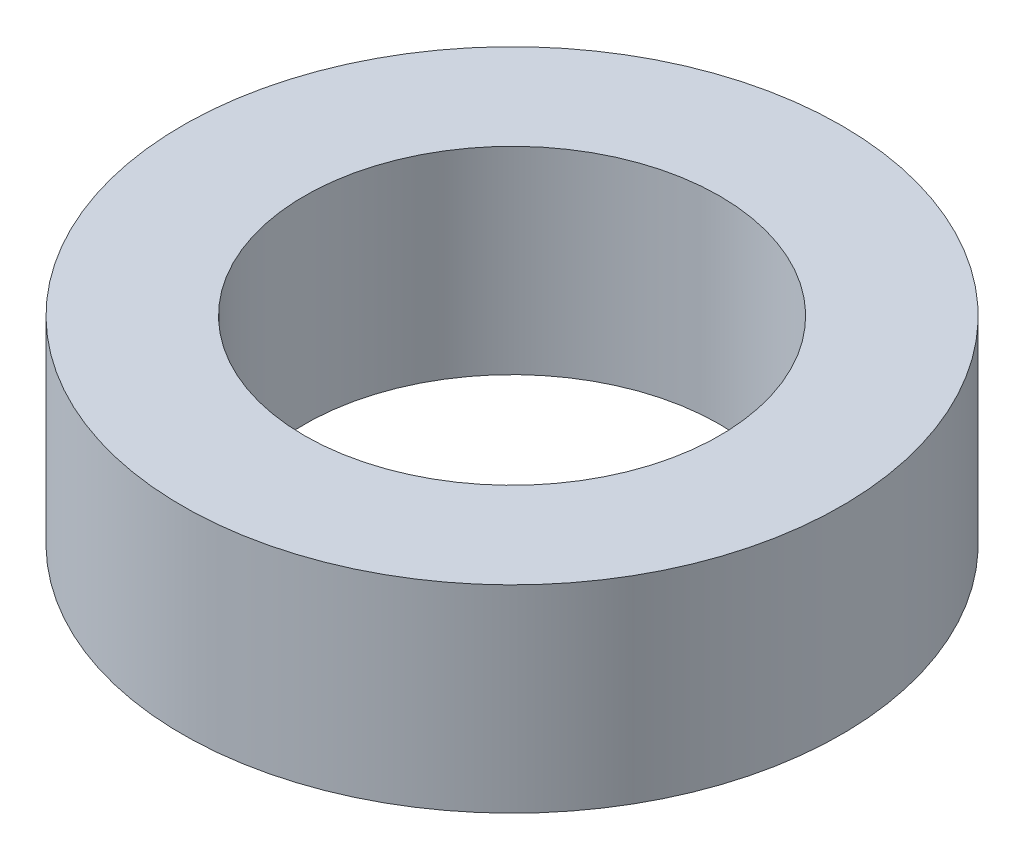
SolidWorks part; units mm, degrees
ref_plane "Front Plane" through (0, 0, 0) normal (0, 0, 1) x (1, 0, 0)
ref_plane "Top Plane" through (0, 0, 0) normal (0, 1, 0) x (1, 0, 0)
ref_plane "Right Plane" through (0, 0, 0) normal (1, 0, 0) x (0, 0, -1)
sketch "Sketch1" plane through (0, 0, 0) normal (0, 1, 0) x (1, 0, 0)
  circle A0 centre (0, 0) radius 6.35
  dimension "D1" = 12.7
extrude "Boss-Extrude1" add sketch "Sketch1" along normal blind 3.81
sketch "Sketch2" plane through (0, 3.81, 0) normal (0, 1, 0) x (1, 0, 0)
  circle A0 centre (0, 0) radius 4
  dimension "D1" = 8
sketch "Sketch3" plane through (0, 3.81, 0) normal (0, 1, 0) x (1, 0, 0)
  circle A0 centre (0, 0) radius 4
  dimension "D1" = 8
extrude "Cut-Extrude2" cut sketch "Sketch3" against normal through all
